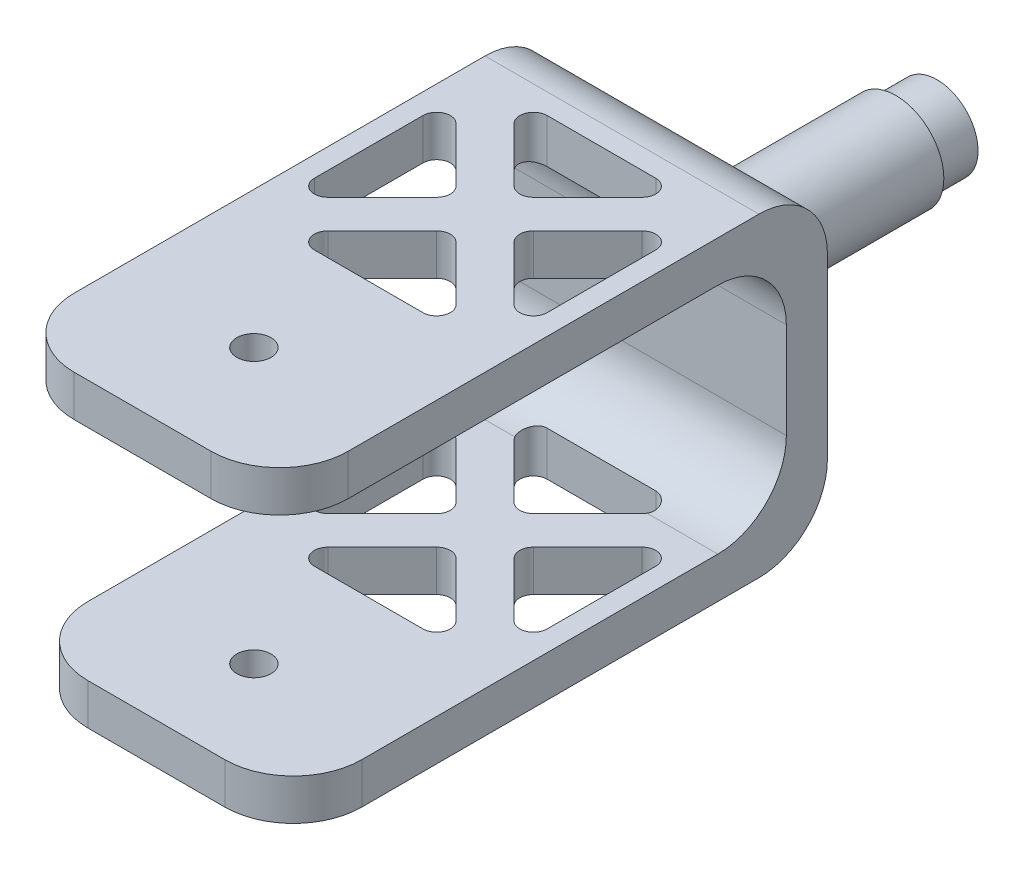
SolidWorks part; units mm, degrees
ref_plane "Front Plane" through (0, 0, 0) normal (0, 0, 1) x (1, 0, 0)
ref_plane "Top Plane" through (0, 0, 0) normal (0, 1, 0) x (1, 0, 0)
ref_plane "Right Plane" through (0, 0, 0) normal (1, 0, 0) x (0, 0, -1)
sketch "Sketch1" plane through (0, 0, 0) normal (0, 1, 0) x (1, 0, 0)
  line L0 (0, 31.8779) -> (0, -8.1221)
  line L1 (10, -8.1221) -> (-10, -8.1221)
  line L2 (10, -8.1221) -> (10, 31.8779)
  line L3 (10, 31.8779) -> (-10, 31.8779)
  line L4 (-10, -8.1221) -> (-10, 31.8779)
  circle A0 centre (0, 0) radius 1.25
  circle A1 centre (0, 0) radius 22.775 construction
  dimension "D1" = 2.5
  dimension "D2" = 45.55
  dimension "D3" = 40
  dimension "D4" = 20
extrude "Boss-Extrude1" add sketch "Sketch1" along normal blind 3 contours A0 L0 L1 L2 L3 | A0 L0 L3 L4 L1 region at (5.0276, 0, -11.9513) region at (-5.0276, 0, -11.9513)
sketch "Sketch2" plane through (0, 0, 0) normal (0, -1, 0) x (1, 0, 0)
  line L0 (10, 8.1221) -> (10, -31.8779) construction
  line L1 (-10, -31.8779) -> (10, -31.8779)
  line L2 (-10, -31.8779) -> (-10, -28.8779)
  line L3 (-10, -28.8779) -> (10, -28.8779)
  line L4 (10, -31.8779) -> (10, -28.8779)
  dimension "D1" = 3
extrude "Boss-Extrude2" add sketch "Sketch2" along normal blind 20
sketch "Sketch3" plane through (0, 0, -28.8779) normal (0, 0, 1) x (1, 0, 0)
  line L0 (10, -20) -> (-10, -20) construction
  line L1 (-10, -20) -> (10, -20)
  line L2 (-10, -20) -> (-10, -17)
  line L3 (-10, -17) -> (10, -17)
  line L4 (10, -20) -> (10, -17)
  line L5 (-10, -20) -> (-10, 0) construction
  line L6 (10, -20) -> (10, 0) construction
  dimension "D1" = 3
extrude "Boss-Extrude3" add sketch "Sketch3" along normal blind 36
fillet "Fillet1" radius 5 6 edges at (0, 3, -31.8779) (0, -20, -31.8779) (10, -18.5, 7.1221) (-10, -18.5, 7.1221) (10, 1.5, 8.1221) (-10, 1.5, 8.1221)
fillet "Fillet2" radius 5 2 edges at (0, -17, -28.8779) (0, 0, -28.8779)
sketch "Sketch4" plane through (0, 3, 0) normal (0, 1, 0) x (1, 0, 0)
  circle A0 centre (0, 0) radius 1.25
  dimension "D1" = 2.5
extrude "Cut-Extrude1" cut sketch "Sketch4" against normal blind 36
sketch "Sketch5" plane through (0, 0, -31.8779) normal (0, 0, -1) x (-1, 0, 0)
  circle A0 centre (0, -8) radius 3.5
  dimension "D1" = 7
extrude "Boss-Extrude4" add sketch "Sketch5" along normal blind 18
sketch "Sketch6" plane through (0, 0, -49.8779) normal (0, 0, -1) x (-1, 0, 0)
  circle A0 centre (0, -8) radius 2.25
  dimension "D1" = 4.5
extrude "Cut-Extrude2" cut sketch "Sketch6" against normal blind 3.9
fillet "Fillet3" [suppressed] radius 2.4
sketch "Sketch7" plane through (0, 0, -49.8779) normal (0, 0, -1) x (-1, 0, 0)
  circle A0 centre (0, -8) radius 3
  circle A1 centre (0, -8) radius 3.5
  dimension "D1" = 6
extrude "Cut-Extrude3" cut sketch "Sketch7" against normal blind 3
sketch "Sketch8" plane through (0, 3, 0) normal (0, 1, 0) x (1, 0, 0)
  line L0 (-10, 26.8779) -> (10, 26.8779) construction
  line L1 (-10, 28.3779) -> (10, 28.3779)
  line L2 (-10, 25.3779) -> (10, 25.3779)
  line L3 (-10, 6.8779) -> (10, 6.8779) construction
  line L4 (-10, -3.1221) -> (-10, 26.8779) construction
  line L5 (10, -3.1221) -> (10, 26.8779) construction
  line L6 (-10, 8.3779) -> (10, 8.3779)
  line L7 (-10, 5.3779) -> (10, 5.3779)
  line L8 (5, -8.1221) -> (-5, -8.1221) construction
  line L9 (-10, 26.8779) -> (-10, 6.8779) construction
  line L10 (-8.5, 26.8779) -> (-8.5, 6.8779)
  line L11 (-11.5, 26.8779) -> (-11.5, 6.8779)
  line L12 (10, 26.8779) -> (10, 6.8779) construction
  line L13 (11.5, 26.8779) -> (11.5, 6.8779)
  line L14 (8.5, 26.8779) -> (8.5, 6.8779)
  line L15 (-10, 6.8779) -> (10, 26.8779) construction
  line L16 (-11.0607, 7.9386) -> (8.9393, 27.9386)
  line L17 (-8.9393, 5.8173) -> (11.0607, 25.8173)
  line L18 (10, 6.8779) -> (-10, 26.8779) construction
  line L19 (8.9393, 5.8173) -> (-11.0607, 25.8173)
  line L20 (11.0607, 7.9386) -> (-8.9393, 27.9386)
  arc A0 (-10, 28.3779) -> (-10, 25.3779) centre (-10, 26.8779) ccw
  arc A1 (10, 25.3779) -> (10, 28.3779) centre (10, 26.8779) ccw
  arc A2 (-10, 8.3779) -> (-10, 5.3779) centre (-10, 6.8779) ccw
  arc A3 (10, 5.3779) -> (10, 8.3779) centre (10, 6.8779) ccw
  arc A4 (-8.5, 26.8779) -> (-11.5, 26.8779) centre (-10, 26.8779) ccw
  arc A5 (-11.5, 6.8779) -> (-8.5, 6.8779) centre (-10, 6.8779) ccw
  arc A6 (11.5, 26.8779) -> (8.5, 26.8779) centre (10, 26.8779) ccw
  arc A7 (8.5, 6.8779) -> (11.5, 6.8779) centre (10, 6.8779) ccw
  arc A8 (-11.0607, 7.9386) -> (-8.9393, 5.8173) centre (-10, 6.8779) ccw
  arc A9 (11.0607, 25.8173) -> (8.9393, 27.9386) centre (10, 26.8779) ccw
  arc A10 (8.9393, 5.8173) -> (11.0607, 7.9386) centre (10, 6.8779) ccw
  arc A11 (-8.9393, 27.9386) -> (-11.0607, 25.8173) centre (-10, 26.8779) ccw
  point P4 (0, 26.8779)
  point P9 (0, 6.8779)
  point P20 (-10, 16.8779)
  point P29 (10, 16.8779)
  point P38 (0, 16.8779)
  point P43 (0, 16.8779)
  dimension "D1" = 1.5
  dimension "D2" = 1.5
  dimension "D3" = 15
extrude "Cut-Extrude4" cut sketch "Sketch8" against normal blind 40 contours L16 L19 L10 | L20 L16 L2 | L20 L14 L17 | L6 L19 L17 region at (0, 3, -23.2517) region at (-6.3738, 3, -16.8779) region at (6.3738, 3, -16.8779) region at (0, 3, -10.5042)
fillet "Fillet4" radius 1 24 edges at (-6.3787, 1.5, -8.3779) (0, 1.5, -14.7566) (6.3787, 1.5, -8.3779) (8.5, 1.5, -10.4992) (8.5, 1.5, -23.2566) (2.1213, 1.5, -16.8779) (-8.5, 1.5, -23.2566) (-2.1213, 1.5, -16.8779) (-8.5, 1.5, -10.4992) (-6.3787, 1.3848, -25.3779) (6.3787, 1.3848, -25.3779) (0, 1.5, -18.9992) (-8.5, -18.5, -10.4992) (-2.1213, -18.5, -16.8779) (-8.5, -18.5, -23.2566) (0, -18.5, -14.7566) (-6.3787, -18.5, -8.3779) (6.3787, -18.5, -8.3779) (8.5, -18.5, -10.4992) (8.5, -18.5, -23.2566) (2.1213, -18.5, -16.8779) (0, -18.5, -18.9992) (-6.3787, -18.3848, -25.3779) (6.3787, -18.3848, -25.3779)
fillet "Fillet5" radius 1 1 edges at (3.5, -8, -31.8779)
